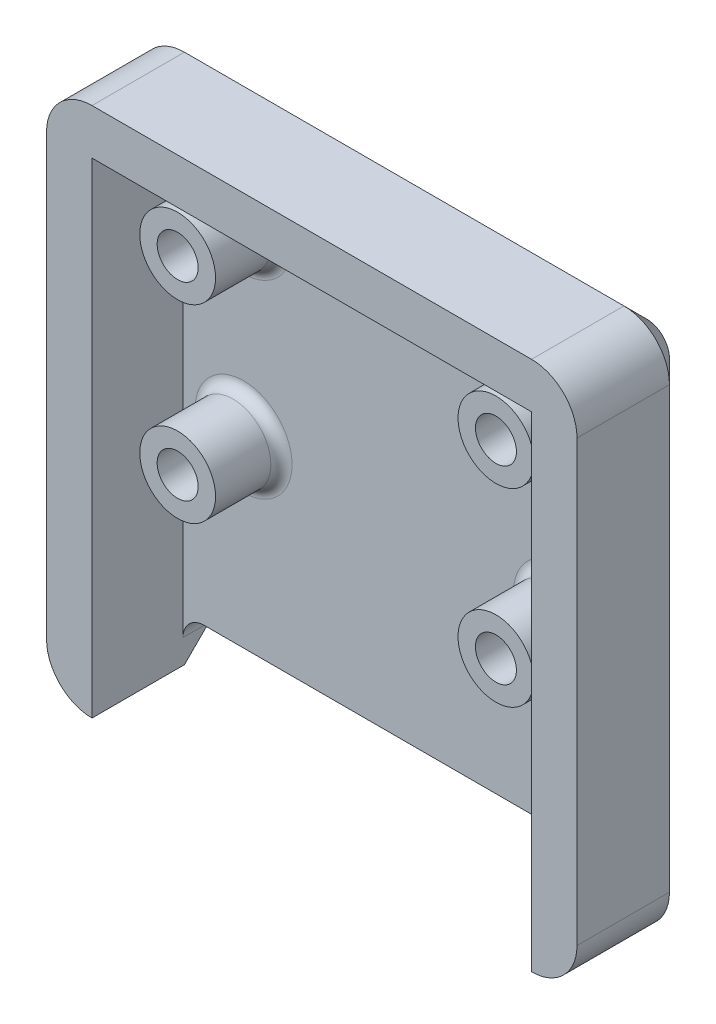
SolidWorks part; units mm, degrees
ref_plane "Front" through (0, 0, 0) normal (0, 0, 1) x (1, 0, 0)
ref_plane "Top" through (0, 0, 0) normal (0, 1, 0) x (1, 0, 0)
ref_plane "Right" through (0, 0, 0) normal (1, 0, 0) x (0, 0, -1)
sketch "Sketch1" plane through (0, 0, 0) normal (0, 0, 1) x (1, 0, 0)
  line L0 (-17.5, -14.5) -> (-17.5, 14.5)
  line L1 (14.5, -14.5) -> (-14.5, -14.5)
  line L2 (14.5, -14.5) -> (14.5, 14.5)
  line L3 (14.5, 14.5) -> (-14.5, 14.5)
  line L4 (-14.5, -14.5) -> (-14.5, 14.5)
  line L5 (0, 14.5) -> (0, -14.5) construction
  line L6 (14.5, 0) -> (-14.5, 0) construction
  line L7 (14.5, 17.5) -> (-14.5, 17.5)
  line L8 (17.5, -14.5) -> (17.5, 14.5)
  line L9 (14.5, -17.5) -> (-14.5, -17.5)
  line L10 (-17.5, -17.5) -> (-17.5, 17.5) construction
  line L11 (17.5, -17.5) -> (-17.5, -17.5) construction
  line L12 (17.5, -17.5) -> (17.5, 17.5) construction
  line L13 (17.5, 17.5) -> (-17.5, 17.5) construction
  line L14 (-14.5, -14.5) -> (-14.5, -17.5)
  line L15 (12.5, -12) -> (-12.5, -12) construction
  line L16 (12.5, -12) -> (12.5, 12) construction
  line L17 (12.5, 12) -> (-12.5, 12) construction
  line L18 (-12.5, -12) -> (-12.5, 12) construction
  line L19 (0, 12) -> (0, -12) construction
  line L20 (12.5, 0) -> (-12.5, 0) construction
  line L21 (14.5, -14.5) -> (14.5, -17.5)
  arc A0 (-17.5, -14.5) -> (-14.5, -17.5) centre (-14.5, -14.5) ccw
  arc A1 (17.5, -14.5) -> (14.5, -17.5) centre (14.5, -14.5) cw
  arc A2 (14.5, 17.5) -> (17.5, 14.5) centre (14.5, 14.5) cw
  arc A3 (-17.5, 14.5) -> (-14.5, 17.5) centre (-14.5, 14.5) cw
  point P0 (0, 0)
  point P23 (0, 0)
  dimension "D3" = 3
  dimension "D1" = 29
  dimension "D2" = 3
  dimension "D4" = 24
  dimension "D5" = 25
extrude "Boss-Extrude1" add sketch "Sketch1" against normal blind 1.6 contours L4 L1 L2 L3 | A3 L0 A0 L9 A1 L8 A2 L7 L1 L4 L3 L2 region at (-17.005, 0, 0) region at (0, 0, 0)
extrude "Boss-Extrude2" add sketch "Sketch1<3>" along normal blind 6 contours A3 L0 A0 L14 L4 L3 L2 L21 A1 L8 A2 L7 region at (-17.005, 0, 0)
sketch "Sketch1<3>" plane through (0, 0, 0) normal (0, 0, 1) x (1, 0, 0) same geometry as "Sketch1"
sketch "Sketch3" plane through (0, 0, 0) normal (0, 0, 1) x (1, 0, 0)
  line L0 (-12.5, -12) -> (-12.5, 12) construction
  line L2 (12.5, -12) -> (12.5, 12) construction
  line L3 (12.5, 12) -> (-12.5, 12) construction
  line L4 (12.5, -12) -> (-12.5, -12) construction
  line L5 (12.5, -12) -> (12.5, 12) construction
  line L6 (12.5, 12) -> (-12.5, 12) construction
  line L7 (-12.5, -12) -> (-12.5, 12) construction
  line L8 (12.5, -12) -> (-12.5, -12) construction
  line L9 (-12.5, 12) -> (12.5, -12) construction
  line L10 (12.5, 12) -> (-12.5, -12) construction
  line L11 (12.5, -2.42) -> (-12.5, -2.42) construction
  point P1 (-10.5, 10.08)
  point P4 (10.5, 10.08)
  point P6 (10.5, -2.42)
  point P7 (-10.5, -2.42)
  dimension "D1" = 2
  dimension "D2" = 12.5
hole_wizard "CSK for #2 Flat Head Machine Screw (100)1" positions "Sketch4" profile "Sketch6" countersink size "#2" standard "ANSI Inch" end condition through all
sketch "Sketch4" plane through (0, 0, -1.6) normal (0, 0, -1) x (-1, 0, 0)
  point P0 (10.5, 10.08)
  point P3 (10.5, -2.42)
  point P6 (-10.5, 10.08)
  point P9 (-10.5, -2.42)
sketch "Sketch6" plane through (-10.5, 10.08, -1.6) normal (1, 0, 0) x (0, 1, 0)
  line L0 (0, 0) -> (0, 7.6)
  line L1 (0, 7.6) -> (1.3525, 7.6)
  line L2 (1.3525, 7.6) -> (1.3525, 0.698)
  line L3 (1.3525, 0.698) -> (2.1844, 0)
  line L5 (2.1844, 0) -> (0, 0)
  line L6 (-1.3525, 0.698) -> (-2.1844, 0) construction
  line L11 (0, -6.35) -> (0, 107.95) construction
  dimension "Thru Hole Dia." = 2.7051
  dimension "Thru Hole Depth" = 7.6
  dimension "Near C'Sink Dia." = 4.3688
  dimension "Near C'Sink Angle" = 100
sketch "Sketch7" plane through (0, 0, 0) normal (0, 0, 1) x (1, 0, 0)
  circle A0 centre (-10.5, 10.08) radius 1.3525
  circle A1 centre (-10.5, 10.08) radius 2.5
  circle A2 centre (-10.5, 10.08) radius 1.3525 construction
  circle A3 centre (10.5, 10.08) radius 1.3525
  circle A5 centre (10.5, 10.08) radius 2.5
  circle A6 centre (10.5, -2.42) radius 1.3526
  circle A7 centre (10.5, -2.42) radius 2.5
  circle A8 centre (-10.5, -2.42) radius 1.3525
  circle A9 centre (-10.5, -2.42) radius 2.5
  dimension "D1" = 5
extrude "Boss-Extrude3" add sketch "Sketch7" along normal offset from surface (4.35 mm away) 1.65 up to face at (0, 2.9, 6)
fillet "Fillet1" radius 0.7 4 edges at (13, -2.42, 0) (-8, -2.42, 0) (13, 10.08, 0) (-8, 10.08, 0)
fillet "Fillet3" radius 1.4 2 edges at (-14.5, -14.5, -0.8) (14.5, -14.5, -0.8)
chamfer "Chamfer1" distance 1.5 angle 45 7 edges at (16.6213, -16.6213, -1.6) (-16.6213, -16.6213, -1.6) (17.5, 0, -1.6) (-17.5, 0, -1.6) (16.6213, 16.6213, -1.6) (-16.6213, 16.6213, -1.6) (0, 17.5, -1.6)
